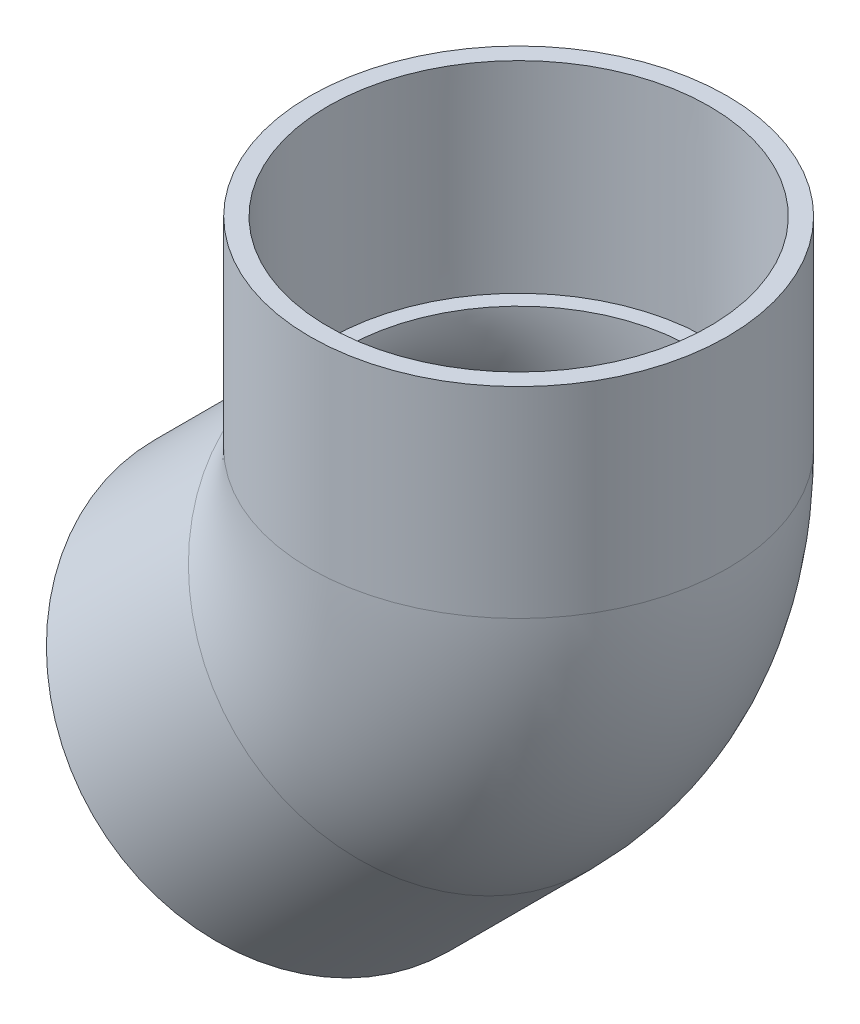
SolidWorks part; units mm, degrees
material "PVC 0.007 Plasticized"
ref_plane "Front Plane" through (0, 0, 0) normal (0, 0, 1) x (1, 0, 0)
ref_plane "Top Plane" through (0, 0, 0) normal (0, 1, 0) x (1, 0, 0)
ref_plane "Right Plane" through (0, 0, 0) normal (1, 0, 0) x (0, 0, -1)
sketch "ElbowArc" plane through (0, 0, 0) normal (0, 0, 1) x (1, 0, 0)
  line L0 (-95.9765, -95.9765) -> (0, 0) construction
  line L1 (0, 0) -> (0, 135.7312) construction
  line L2 (-33.1147, -33.1147) -> (0, 0) construction
  line L3 (0, 0) -> (0, 46.8312) construction
  line L4 (-161.2629, -30.69) -> (-30.69, -161.2629) construction
  line L5 (-92.5101, 26.2807) -> (-155.6682, -36.2847) construction
  line L6 (-92.5101, 26.2807) -> (26.2807, -92.5101) construction
  line L7 (26.2807, -92.5101) -> (-36.2847, -155.6682) construction
  line L8 (-155.6682, -36.2847) -> (-36.2847, -155.6682) construction
  line L9 (-92.329, 135.7312) -> (92.329, 135.7312) construction
  line L10 (-84.4169, 135.7312) -> (84.4169, 135.7312) construction
  line L11 (84.4169, 135.7312) -> (83.9978, 46.8312) construction
  line L12 (83.9978, 46.8312) -> (-83.9978, 46.8312) construction
  line L13 (-83.9978, 46.8312) -> (-84.4169, 135.7312) construction
  line L14 (-87.5799, 21.3506) -> (21.3506, -87.5799) construction
  line L18 (-77.0255, 46.8312) -> (77.0255, 46.8312) construction
  arc A0 (0, 46.8312) -> (-33.1147, -33.1147) centre (-113.0606, 46.8313) cw construction
  dimension "D1" = 113.0606
  dimension "BendRadius" = 135.7312
  dimension "J" = 46.8312
  dimension "M" = 184.658
  dimension "OD A" = 168.8338
  dimension "OD B" = 167.9956
  dimension "ID" = 154.051
  dimension "BendAngle" = 45
sketch "Sketch1" plane through (0, 0, 0) normal (0, 0, 1) x (1, 0, 0)
  line L0 (-95.9765, -95.9765) -> (0, 0) construction
  line L1 (-95.9765, -95.9765) -> (0, 0) construction
  line L3 (-30.69, -161.2629) -> (32.1718, -98.4012)
  line L4 (-30.69, -161.2629) -> (-36.2847, -155.6682)
  line L5 (-36.2847, -155.6682) -> (26.2807, -92.5101)
  line L6 (32.1718, -98.4012) -> (26.2807, -92.5101)
revolve "Revolve1" add sketch "Sketch1" angle 360 about L1
sketch "Sketch2" plane through (0, 0, 0) normal (0, 0, 1) x (1, 0, 0)
  line L0 (84.4169, 135.7312) -> (83.9978, 46.8312)
  line L1 (83.9978, 46.8312) -> (92.329, 46.8312)
  line L2 (92.329, 46.8312) -> (92.329, 135.7312)
  line L3 (92.329, 135.7312) -> (84.4169, 135.7312)
  line L4 (0, 0) -> (0, 135.7312) construction
  line L5 (0, 0) -> (0, 135.7312) construction
revolve "Revolve2" add sketch "Sketch2" angle 360 about L5
sketch "Sketch3" plane through (-33.1147, -33.1147, 0) normal (0.7071, 0.7071, 0) x (0, 0, -1)
  circle A0 centre (0, 0) radius 77.0255
  circle A1 centre (0, 0) radius 92.329
sketch "Sketch4" plane through (0, 0, 0) normal (0, 0, 1) x (1, 0, 0)
  line L0 (-95.9765, -95.9765) -> (0, 0) construction
  line L1 (0, 0) -> (0, 135.7312) construction
  line L2 (-95.9765, -95.9765) -> (-33.1147, -33.1147) construction
  line L3 (0, 46.8313) -> (0, 135.7312) construction
  arc A0 (-33.1147, -33.1147) -> (0, 46.8313) centre (-113.0606, 46.8313) ccw
sweep "Sweep1" add profiles "Sketch3" path "Sketch4"
other "CPoint1" parameters "Diameter"=152.4, "StubLength"=38.1
ref_axis "Axis1" through (0, 56.8313, 0) along (0, -1, 0)
other "CPoint2" parameters "Diameter"=152.4, "StubLength"=228.6
ref_axis "Axis2" through (-40.1858, -40.1858, 0) along (0.7071, 0.7071, 0)
